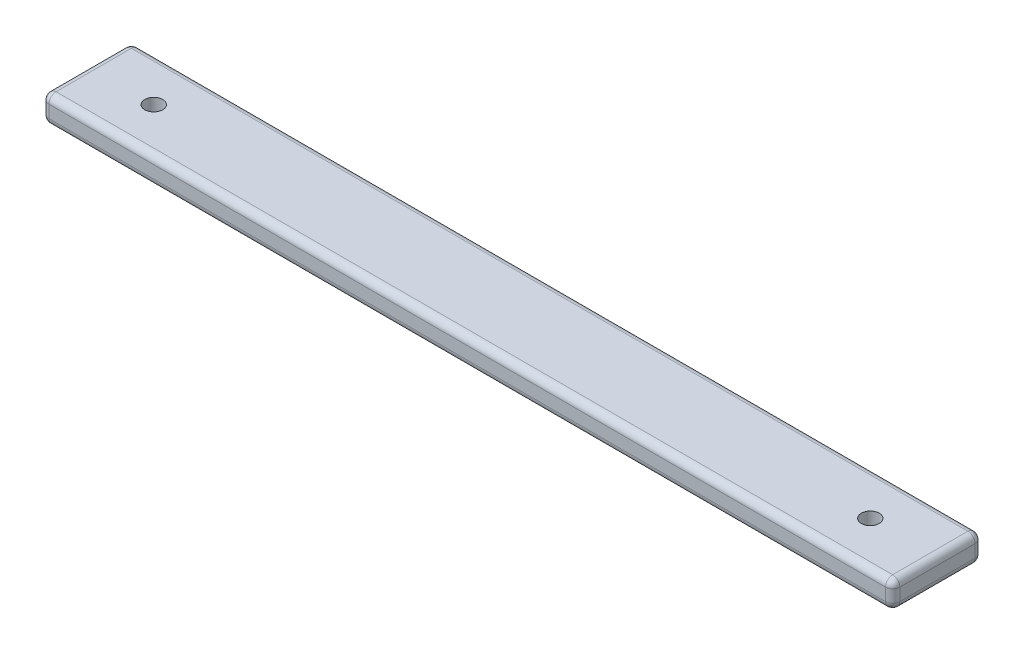
SolidWorks part; units mm, degrees
ref_plane "Front Plane" through (0, 0, 0) normal (0, 0, 1) x (1, 0, 0)
ref_plane "Top Plane" through (0, 0, 0) normal (0, 1, 0) x (1, 0, 0)
ref_plane "Right Plane" through (0, 0, 0) normal (1, 0, 0) x (0, 0, -1)
sketch "Sketch1" plane through (0, 0, 0) normal (0, 1, 0) x (1, 0, 0)
  line L1 (-47.5, 5) -> (47.5, 5)
  line L2 (-47.5, 5) -> (-47.5, -5)
  line L3 (-47.5, -5) -> (47.5, -5)
  line L4 (47.5, 5) -> (47.5, -5)
  line L5 (-47.5, 5) -> (47.5, -5) construction
  line L6 (-47.5, -5) -> (47.5, 5) construction
  point P0 (0, 0)
  dimension "D1" = 10
  dimension "D2" = 95
extrude "Boss-Extrude1" add sketch "Sketch1" along normal blind 3
fillet "Fillet1" radius 0.8 8 edges at (0, 0, -5) (-47.5, 0, 0) (0, 0, 5) (47.5, 0, 0) (0, 3, 5) (-47.5, 3, 0) (0, 3, -5) (47.5, 3, 0)
fillet "Fillet2" radius 0.8 12 edges at (-47.2657, 2.7657, 4.7657) (-47.2657, 0.2343, 4.7657) (-47.2657, 2.7657, -4.7657) (-47.2657, 0.2343, -4.7657) (47.2657, 2.7657, 4.7657) (47.2657, 0.2343, 4.7657) (47.2657, 2.7657, -4.7657) (47.2657, 0.2343, -4.7657) (-47.5, 1.5, 5) (-47.5, 1.5, -5) (47.5, 1.5, 5) (47.5, 1.5, -5)
sketch "Sketch2" plane through (0, 3, 0) normal (0, 1, 0) x (1, 0, 0)
  line L0 (-51.3053, 0) -> (51.1922, 0) construction
  line L1 (-40, 0) -> (40, 0) construction
  circle A0 centre (0, 0) radius 1
  circle A1 centre (-40, 0) radius 1
  circle A2 centre (40, 0) radius 1
  dimension "D1" = 2
  dimension "D3" = 2
  dimension "D4" = 2
  dimension "D2" = 80
extrude "Cut-Extrude1" cut sketch "Sketch2" against normal through all
sketch "Sketch3" plane through (0, 3, 0) normal (0, 1, 0) x (1, 0, 0)
  circle A2 centre (0, 0) radius 1
  circle A3 centre (0, 0) radius 1
  dimension "D1" = 0
extrude "Boss-Extrude2" add sketch "Sketch3" against normal blind 5
sketch "Sketch4" plane through (0, -2, 0) normal (0, -1, 0) x (1, 0, 0)
  circle A2 centre (0, 0) radius 0.6786
  circle A5 centre (0, 0) radius 1
  circle A6 centre (0, 0) radius 1
  circle M2 centre (0, 0) radius 1
  dimension "D1" = 0
extrude "Cut-Extrude3" cut sketch "Sketch4" against normal up to surface (2 mm away) contours A2 M2 region at (-0.9717, -2, 0) up to face at (40, 0, 1)
